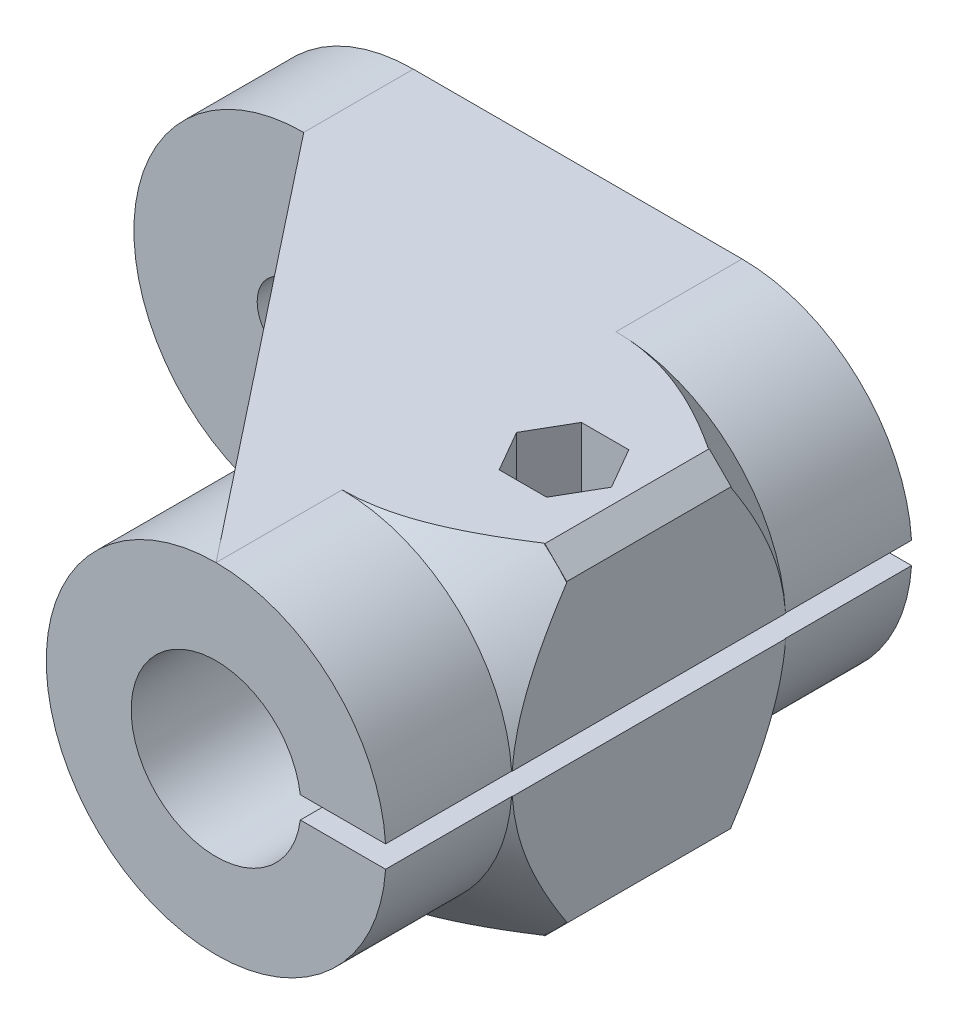
SolidWorks part; units mm, degrees
ref_plane "Front Plane" through (0, 0, 0) normal (0, 0, 1) x (1, 0, 0)
ref_plane "Top Plane" through (0, 0, 0) normal (0, 1, 0) x (1, 0, 0)
ref_plane "Right Plane" through (0, 0, 0) normal (1, 0, 0) x (0, 0, -1)
sketch "Sketch1" plane through (0, 0, 0) normal (0, 0, 1) x (1, 0, 0)
  line L0 (0, 15.5) -> (-30, 15.5)
  line L1 (-30, -15.5) -> (0, -15.5)
  line L2 (-31, 0) -> (-29, 0) construction
  line L3 (-31, 3.25) -> (-29, 3.25)
  line L4 (-31, -3.25) -> (-29, -3.25)
  circle A0 centre (0, 0) radius 7.75
  arc A1 (0, -15.5) -> (15.5, 0) centre (0, 0) ccw
  arc A2 (-31, 3.25) -> (-31, -3.25) centre (-31, 0) ccw
  arc A3 (-45.5, 0) -> (-30, -15.5) centre (-30, 0) ccw
  arc A4 (0, 15.5) -> (15.5, 0) centre (0, 0) cw
  arc A5 (-30, 15.5) -> (-45.5, 0) centre (-30, 0) ccw
  arc A6 (-29, -3.25) -> (-29, 3.25) centre (-29, 0) ccw
  point P10 (-30, 0)
  dimension "D1" = 15.5
  dimension "D2" = 31
  dimension "D4" = 3.25
  dimension "D3" = 30
  dimension "D5" = 2
extrude "Boss-Extrude1" add sketch "Sketch1" along normal blind 48
ref_plane "Plane1" through (0, 0, -2.2) normal (0, 0, -1) x (-1, 0, 0)
sketch "Sketch4" plane through (0, 0, 48) normal (0, 0, 1) x (1, 0, 0)
  line L2 (0, 15.5) -> (-30, 15.5)
  line L3 (-30, -15.5) -> (0, -15.5)
  line L4 (0, 15.5) -> (-30, 15.5)
  line L5 (-30, -15.5) -> (0, -15.5)
  arc A0 (0, 15.5) -> (0, -15.5) centre (0, 0) ccw
  arc A2 (0, -15.5) -> (0, 15.5) centre (0, 0) ccw
  arc A3 (-30, 15.5) -> (-30, -15.5) centre (-30, 0) ccw
  arc A5 (-30, 15.5) -> (-30, -15.5) centre (-30, 0) ccw
  dimension "D1" = 0
extrude "Cut-Extrude2" cut sketch "Sketch4" against normal blind 38
sketch "Sketch10" plane through (0, 15.5, 0) normal (0, 1, 0) x (1, 0, 0)
  line L0 (-30, 0) -> (0, 0)
  line L1 (0, 0) -> (0, -48)
  line L2 (0, -48) -> (-30, -10)
  line L3 (-30, -10) -> (-30, 0)
  point P5 (0, 0)
extrude "Boss-Extrude4" add sketch "Sketch10" against normal blind 3
mirror "Mirror3" about plane through (0, 0, 0) normal (0, 1, 0) of "Boss-Extrude4"
ref_plane "Plane3" through (0, 0, 24) normal (0, 0, 1) x (1, 0, 0)
sketch "Sketch11" plane through (0, 0, 24) normal (0, 0, 1) x (1, 0, 0)
  line L0 (0, 15.5) -> (15.5, 15.5)
  line L1 (15.5, 15.5) -> (15.5, 0)
  line L2 (15.5, 0) -> (15.5, -15.5)
  line L3 (15.5, -15.5) -> (0, -15.5)
  arc A0 (0, -15.5) -> (0, 15.5) centre (0, 0) ccw
  arc A1 (0, -15.5) -> (0, 15.5) centre (0, 0) ccw
extrude "Boss-Extrude5" add sketch "Sketch11" along normal mid plane 15 contours A1 L1 L0 | A1 L3 L2 region at (12.0378, -12.0378, 24) region at (12.0378, 12.0378, 24)
sketch "Sketch12" plane through (0, -15.5, 0) normal (0, -1, 0) x (-1, 0, 0)
  line L0 (0, -31.5) -> (-15.5, -16.5) construction
  circle A0 centre (-7.75, -24) radius 2.25
  dimension "D1" = 4.5
extrude "Cut-Extrude6" cut sketch "Sketch12" against normal blind 40
sketch "Sketch13" plane through (0, 15.5, 0) normal (0, 1, 0) x (1, 0, 0)
  line L1 (3.4199, -24) -> (5.5849, -27.75)
  line L2 (5.5849, -27.75) -> (9.9151, -27.75)
  line L3 (9.9151, -27.75) -> (12.0801, -24)
  line L4 (12.0801, -24) -> (9.9151, -20.25)
  line L5 (9.9151, -20.25) -> (5.5849, -20.25)
  line L6 (5.5849, -20.25) -> (3.4199, -24)
  circle A0 centre (7.75, -24) radius 3.75 construction
  dimension "D1" = 7.5
extrude "Cut-Extrude7" cut sketch "Sketch13" against normal blind 8
sketch "Sketch14" plane through (0, -15.5, 0) normal (0, -1, 0) x (-1, 0, 0)
  circle A0 centre (-7.75, -24) radius 3.75
  dimension "D1" = 7.5
extrude "Cut-Extrude8" cut sketch "Sketch14" against normal blind 10
sketch "Sketch15" plane through (0, 0, 48) normal (0, 0, 1) x (1, 0, 0)
  line L0 (0, 0) -> (30.5287, 0)
extrude "Cut-Extrude-Thin2" cut sketch "Sketch15" against normal blind 63 and the other way through all thin thin type mid plane wall 2
chamfer "Chamfer4" distance 5 angle 45 4 edges at (10.6007, 11.3082, 31.5) (10.6007, -11.3082, 31.5) (10.6007, -11.3082, 16.5) (10.6007, 11.3082, 16.5)
chamfer "Chamfer5" distance 2 angle 45 2 edges at (15.5, 15.5, 24) (15.5, -15.5, 24)
